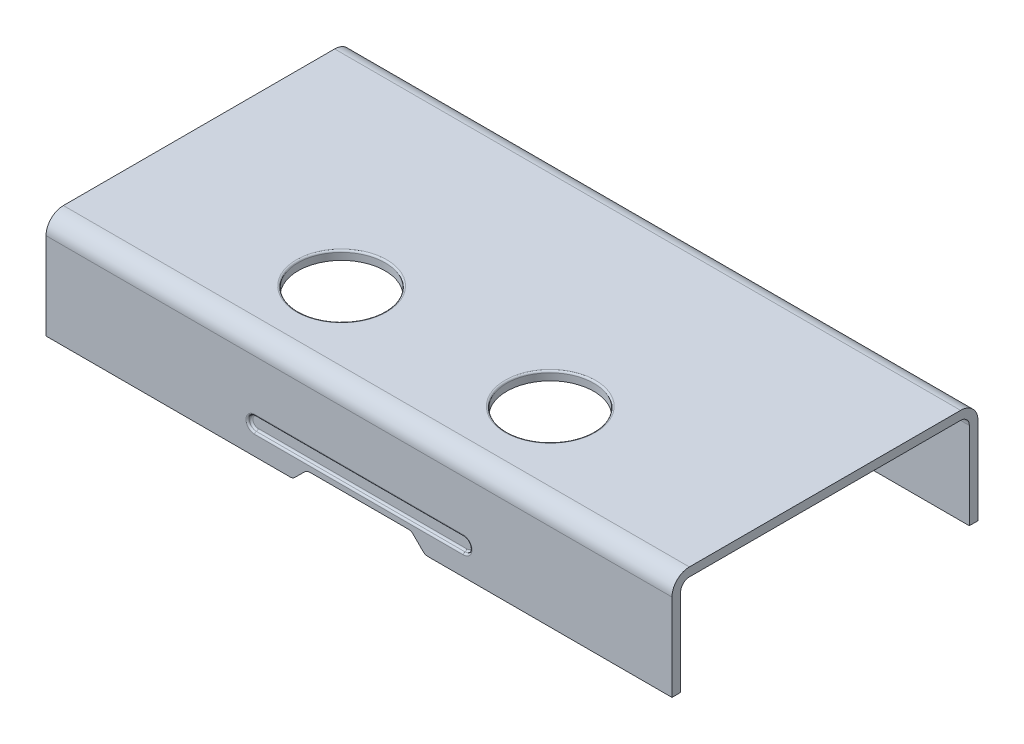
SolidWorks part; units mm, degrees
ref_plane "Front Plane" through (0, 0, 0) normal (0, 0, 1) x (1, 0, 0)
ref_plane "Top Plane" through (0, 0, 0) normal (0, 1, 0) x (1, 0, 0)
ref_plane "Right Plane" through (0, 0, 0) normal (1, 0, 0) x (0, 0, -1)
sketch "Sketch1" plane through (0, 0, 0) normal (0, 1, 0) x (1, 0, 0)
  line L0 (0, -55) -> (0, 55) construction
  line L1 (-9, 4.4) -> (9, 4.4)
  line L2 (-9, 4.4) -> (-9, -4.4)
  line L3 (-9, -4.4) -> (9, -4.4)
  line L4 (9, 4.4) -> (9, -4.4)
  line L5 (-55, 0) -> (55, 0) construction
  dimension "D1" = 18
  dimension "D2" = 9
  dimension "D3" = 8.8
  dimension "D4" = 4.4
extrude "Boss-Extrude1" add sketch "Sketch1" along normal blind 3
sketch "Sketch2" plane through (0, 3, 0) normal (0, 1, 0) x (1, 0, 0)
  line L1 (0, -1.65) -> (0, 1.65) construction
  line L2 (9, 4.4) -> (-9, 4.4) construction
  circle A0 centre (-3, -1.9) radius 1.25
  circle A1 centre (3, -1.9) radius 1.25
  dimension "D1" = 2.5
  dimension "D2" = 2.5
  dimension "D3" = 3
  dimension "D4" = 3
  dimension "D5" = 6.3
  dimension "D6" = 6.3
extrude "Cut-Extrude1" cut sketch "Sketch2" against normal blind 3
fillet "Fillet1" radius 0.5 2 edges at (0, 3, 4.4) (0, 3, -4.4)
sketch "Sketch3" plane through (-9, 0, 0) normal (-1, 0, 0) x (0, 0, 1)
  line L6 (-4.15, 0.25) -> (-4.15, -7.2584)
  line L7 (-4.15, -7.2584) -> (4.15, -7.2584)
  line L8 (4.15, 0.25) -> (4.15, 2.5)
  line L9 (3.9, 2.75) -> (-3.9, 2.75)
  line L10 (-4.15, 2.5) -> (-4.15, 0.25)
  line L11 (-4.15, 0.25) -> (4.15, 0.25)
  line L12 (4.15, 0.25) -> (4.15, 2.5)
  line L13 (3.9, 2.75) -> (-3.9, 2.75)
  line L14 (-4.15, 2.5) -> (-4.15, 0.25)
  line L16 (4.15, 0.25) -> (4.15, -7.2584)
  arc A4 (4.15, 2.5) -> (3.9, 2.75) centre (3.9, 2.5) ccw
  arc A5 (-3.9, 2.75) -> (-4.15, 2.5) centre (-3.9, 2.5) ccw
  arc A6 (4.15, 2.5) -> (3.9, 2.75) centre (3.9, 2.5) ccw
  arc A7 (-3.9, 2.75) -> (-4.15, 2.5) centre (-3.9, 2.5) ccw
  dimension "D1" = 0.25
extrude "Cut-Extrude2" cut sketch "Sketch3" against normal blind 23
sketch "Sketch4" plane through (0, 0, 4.4) normal (0, 0, 1) x (1, 0, 0)
  line L0 (0, -1.65) -> (0, 1.65) construction
  line L1 (-2, -1.0245) -> (2, -1.0245)
  line L2 (-2, -1.0245) -> (-2, 0.4)
  line L3 (-2, 0.4) -> (2, 0.4)
  line L4 (2, -1.0245) -> (2, 0.4)
  line L5 (4.84, 0) -> (-4.84, 0) construction
  dimension "D1" = 4
  dimension "D2" = 2
  dimension "D3" = 0.4
extrude "Cut-Extrude3" cut sketch "Sketch4" against normal blind 2
chamfer "Chamfer1" distance 0.5 angle 45 2 edges at (2, 0.4, 4.275) (-2, 0.4, 4.275)
sketch "Sketch5" plane through (0, 0, 4.4) normal (0, 0, 1) x (1, 0, 0)
  line L0 (-3, 0.8) -> (3, 0.8) construction
  line L1 (-3, 1) -> (3, 1)
  line L2 (-3, 0.6) -> (3, 0.6)
  line L3 (4.84, 0) -> (-4.84, 0) construction
  line L4 (0, -1.65) -> (0, 1.65) construction
  arc A0 (-3, 1) -> (-3, 0.6) centre (-3, 0.8) ccw
  arc A1 (3, 0.6) -> (3, 1) centre (3, 0.8) ccw
  point P2 (0, 0.8)
  dimension "D1" = 0.2
  dimension "D2" = 0.8
  dimension "D3" = 6
  dimension "D4" = 3
extrude "Cut-Extrude4" cut sketch "Sketch5" against normal blind 0.1
fillet "Fillet2" radius 0.05 8 edges at (3.2, 0.8, 4.4) (0, 0.6, 4.4) (-3.2, 0.8, 4.4) (0, 1, 4.3) (3.2, 0.8, 4.3) (0, 0.6, 4.3) (-3.2, 0.8, 4.3) (0, 1, 4.4)
fillet "Fillet3" radius 0.2 4 edges at (1.9, 0, 4.275) (1.5, 0.4, 4.275) (-1.9, 0, 4.275) (-1.5, 0.4, 4.275)
fillet "Fillet4" radius 0.05 2 edges at (3, 3, 3.15) (-3, 3, 3.15)
